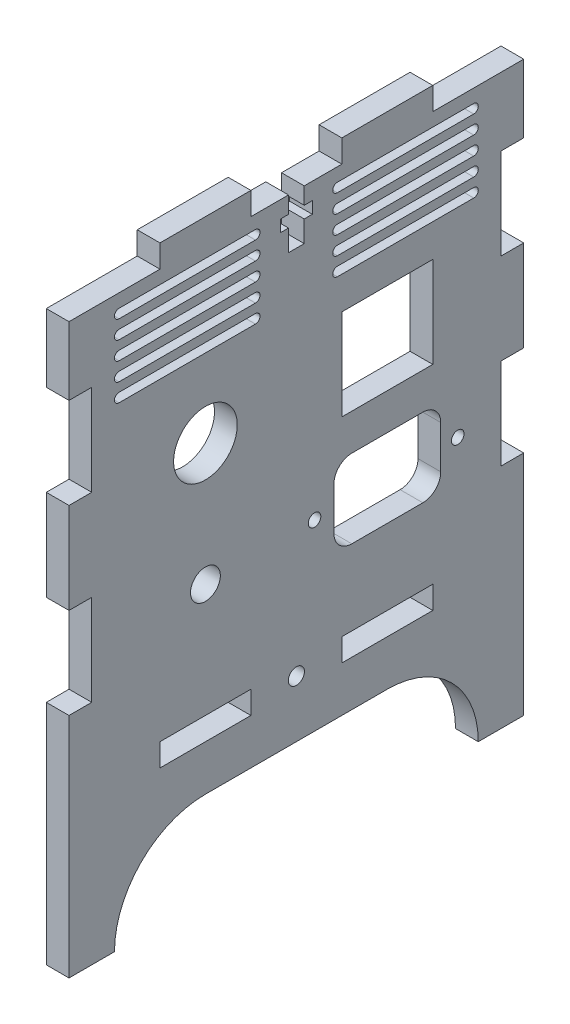
SolidWorks part; units mm, degrees
ref_plane "Front Plane" through (0, 0, 0) normal (0, 0, 1) x (1, 0, 0)
ref_plane "Top Plane" through (0, 0, 0) normal (0, 1, 0) x (1, 0, 0)
ref_plane "Right Plane" through (0, 0, 0) normal (1, 0, 0) x (0, 0, -1)
sketch "Sketch1" plane through (0, 0, 0) normal (1, 0, 0) x (0, 0, -1)
  line L1 (-63.5, 82.55) -> (63.5, 82.55)
  line L2 (-63.5, 82.55) -> (-63.5, -82.55)
  line L3 (-63.5, -82.55) -> (63.5, -82.55)
  line L4 (63.5, 82.55) -> (63.5, -82.55)
  line L5 (-63.5, 82.55) -> (63.5, -82.55) construction
  line L6 (-63.5, -82.55) -> (63.5, 82.55) construction
  point P0 (0, 0)
  dimension "D1" = 127
  dimension "D2" = 165.1
extrude "Boss-Extrude1" add sketch "Sketch1" along normal blind 6.35
sketch "Sketch2" plane through (6.35, 0, 0) normal (1, 0, 0) x (0, 0, -1)
  line L1 (-63.5, 82.55) -> (-38.1, 82.55)
  line L2 (-63.5, 82.55) -> (-63.5, 76.2)
  line L3 (-63.5, 76.2) -> (-38.1, 76.2)
  line L4 (-38.1, 82.55) -> (-38.1, 76.2)
  dimension "D1" = 25.4
  dimension "D2" = 6.35
extrude "Cut-Extrude1" cut sketch "Sketch2" against normal blind 6.35
pattern_linear "LPattern1" count 3 spacing 50.8 along (0, 0, -1) of "Cut-Extrude1"
sketch "Sketch5" plane through (6.35, 0, 0) normal (1, 0, 0) x (0, 0, -1)
  line L0 (-25.4, -82.55) -> (25.4, -82.55) construction
  line L1 (-63.5, -82.55) -> (63.5, -82.55) construction
  line L2 (-25.4, -57.15) -> (25.4, -57.15)
  line L3 (-25.4, -107.95) -> (25.4, -107.95)
  arc A0 (-25.4, -57.15) -> (-25.4, -107.95) centre (-25.4, -82.55) ccw
  arc A1 (25.4, -107.95) -> (25.4, -57.15) centre (25.4, -82.55) ccw
  point P4 (0, -82.55)
  dimension "D2" = 25.4
  dimension "D1" = 50.8
extrude "Cut-Extrude4" cut sketch "Sketch5" against normal blind 6.35
sketch "Sketch8" plane through (6.35, 0, 0) normal (1, 0, 0) x (0, 0, -1)
  line L0 (63.5, -82.55) -> (63.5, 76.2) construction
  line L1 (63.5, 57.15) -> (57.15, 57.15)
  line L2 (63.5, 57.15) -> (63.5, 31.75)
  line L3 (63.5, 31.75) -> (57.15, 31.75)
  line L4 (57.15, 57.15) -> (57.15, 31.75)
  line L5 (38.1, 82.55) -> (12.7, 82.55) construction
  dimension "D1" = 25.4
  dimension "D2" = 25.4
  dimension "D3" = 6.35
extrude "Cut-Extrude6" cut sketch "Sketch8" against normal blind 6.35
pattern_linear "LPattern4" count 2 spacing 50.8 along (0, -1, 0) of "Cut-Extrude6"
ref_plane "Plane1" through (0, 0, 0) normal (0, 0, 1) x (1, 0, 0)
mirror "Mirror1" about plane through (0, 0, 0) normal (0, 0, 1) of "LPattern4"
sketch "Sketch9" plane through (0, 0, 0) normal (-1, 0, 0) x (0, 0, 1)
  line L0 (-63.5, -82.55) -> (-63.5, -19.05) construction
  line L1 (-38.1, -38.1) -> (-12.7, -38.1)
  line L2 (-38.1, -38.1) -> (-38.1, -44.45)
  line L3 (-38.1, -44.45) -> (-12.7, -44.45)
  line L4 (-12.7, -38.1) -> (-12.7, -44.45)
  line L5 (-38.1, 82.55) -> (-12.7, 82.55) construction
  point P6 (-25.4, 82.55)
  dimension "D1" = 25.4
  dimension "D2" = 6.35
  dimension "D3" = 25.4
  dimension "D4" = 120.65
extrude "Cut-Extrude7" cut sketch "Sketch9" against normal blind 6.35
pattern_linear "LPattern6" count 2 spacing 50.8 along (0, 0, 1) of "Cut-Extrude7"
sketch "Sketch16" plane through (0, 0, 0) normal (-1, 0, 0) x (0, 0, 1)
  line L0 (12.7, 76.2) -> (-12.7, 76.2) construction
  line L1 (-2.1971, 76.2) -> (2.1971, 76.2)
  line L2 (-2.1971, 76.2) -> (-2.1971, 62.23)
  line L3 (-2.1971, 62.23) -> (2.1971, 62.23)
  line L4 (2.1971, 76.2) -> (2.1971, 62.23)
  line L5 (-12.7, 76.2) -> (-12.7, 82.55) construction
  line L7 (-4.445, 71.501) -> (4.445, 71.501)
  line L8 (-4.445, 71.501) -> (-4.445, 68.199)
  line L9 (-4.445, 68.199) -> (4.445, 68.199)
  line L10 (4.445, 71.501) -> (4.445, 68.199)
  point P6 (0, 62.23)
  point P13 (0, 71.501)
  point P14 (4.445, 69.85)
  dimension "D1" = 4.3942
  dimension "D2" = 13.97
  dimension "D3" = 12.7
  dimension "D4" = 3.302
  dimension "D5" = 8.89
  dimension "D6" = 12.7
  dimension "D7" = 6.35
extrude "Cut-Extrude14" cut sketch "Sketch16" against normal blind 6.35 contours L7 L10 L9 L8 | L1 L4 L3 L2
hole_wizard "#8 Clearance Hole1" positions "Sketch18" profile "Sketch17" hole size "#8" standard "ANSI Inch"
sketch "Sketch18" plane through (0, 0, 0) normal (-1, 0, 0) x (0, 0, 1)
  line L3 (-12.7, -44.45) -> (-12.7, -38.1) construction
  line L4 (38.1, -38.1) -> (12.7, -38.1) construction
  point P0 (0, -41.275)
  point P16 (-12.7, -41.275)
  dimension "D1" = 12.7
  dimension "D2" = 3.175
sketch "Sketch17" plane through (0, -41.275, 0) normal (0, 1, 0) x (0, 0, 1)
  line L0 (0, 0) -> (0, 11.5107)
  line L1 (0, 11.5107) -> (2.2479, 10.16)
  line L2 (2.2479, 10.16) -> (2.2479, 0)
  line L5 (2.2479, 0) -> (0, 0)
  line L10 (0, 11.5107) -> (-2.2479, 10.16) construction
  line L11 (0, -6.35) -> (0, 107.95) construction
  dimension "Hole Dia." = 4.4958
  dimension "Hole Depth" = 10.16
  dimension "Drill Angle" = 118
sketch "Sketch19" plane through (0, 0, 0) normal (-1, 0, 0) x (0, 0, 1)
  line L0 (-49.53, 71.1789) -> (-11.43, 71.1789) construction
  line L1 (-49.53, 72.4489) -> (-11.43, 72.4489)
  line L2 (-49.53, 69.9089) -> (-11.43, 69.9089)
  line L3 (-38.1, 82.55) -> (-38.1, 76.2) construction
  arc A0 (-49.53, 72.4489) -> (-49.53, 69.9089) centre (-49.53, 71.1789) ccw
  arc A1 (-11.43, 69.9089) -> (-11.43, 72.4489) centre (-11.43, 71.1789) ccw
  point P2 (-30.48, 71.1789)
  point P7 (-30.48, 72.4489)
  dimension "D2" = 1.27
  dimension "D1" = 38.1
  dimension "D3" = 7.62
extrude "Cut-Extrude15" cut sketch "Sketch19" against normal blind 6.35
mirror "Mirror2" about plane through (0, 0, 0) normal (0, 0, 1) of "Cut-Extrude15"
pattern_linear "LPattern7" count 5 spacing 5.08 along (0, -1, 0) of "Mirror2"
sketch "Sketch20" plane through (0, 0, 0) normal (-1, 0, 0) x (0, 0, 1)
  line L1 (-35.3225, 4.9) -> (-15.4775, 4.9)
  line L2 (-40.3225, -0.1) -> (-40.3225, -12.0202)
  line L3 (-35.3225, -17.0202) -> (-15.4775, -17.0202)
  line L4 (-10.4775, -0.1) -> (-10.4775, -12.0202)
  line L5 (-63.5, 6.35) -> (-63.5, 31.75) construction
  circle A0 centre (-45.0725, -6.0601) radius 1.75
  circle A1 centre (-5.0725, -6.0601) radius 1.75
  arc A2 (-40.3225, -12.0202) -> (-35.3225, -17.0202) centre (-35.3225, -12.0202) ccw
  arc A3 (-15.4775, 4.9) -> (-10.4775, -0.1) centre (-15.4775, -0.1) cw
  arc A4 (-15.4775, -17.0202) -> (-10.4775, -12.0202) centre (-15.4775, -12.0202) ccw
  arc A5 (-40.3225, -0.1) -> (-35.3225, 4.9) centre (-35.3225, -0.1) cw
  point P8 (-25.4, 4.9)
  point P13 (-40.3225, -6.0601)
  point P18 (-10.4775, 4.9)
  point P21 (-10.4775, -17.0202)
  point P24 (-40.3225, 4.9)
  dimension "D1" = 3.5
  dimension "D2" = 3.5
  dimension "D10" = 5
  dimension "D11" = 5
  dimension "D12" = 5
  dimension "D13" = 5
  dimension "D3" = 40
  dimension "D4" = 29.845
  dimension "D5" = 21.9202
  dimension "D6" = 38.1
extrude "Cut-Extrude16" cut sketch "Sketch20" against normal blind 7.62
sketch "Sketch22" plane through (0, 0, 0) normal (-1, 0, 0) x (0, 0, 1)
  line L0 (-15.4775, 4.9) -> (-35.3225, 4.9) construction
  line L1 (-38.1, 40.46) -> (-12.7, 40.46)
  line L2 (-38.1, 40.46) -> (-38.1, 15.06)
  line L3 (-38.1, 15.06) -> (-12.7, 15.06)
  line L4 (-12.7, 40.46) -> (-12.7, 15.06)
  point P4 (-25.4, 15.06)
  point P5 (-25.4, 4.9)
  dimension "D1" = 25.4
  dimension "D2" = 25.4
  dimension "D3" = 0
  dimension "D4" = 10.16
extrude "Cut-Extrude17" cut sketch "Sketch22" against normal blind 6.35
sketch "Sketch23" plane through (0, 0, 0) normal (-1, 0, 0) x (0, 0, 1)
  line L0 (-12.7, 15.06) -> (-12.7, 40.46) construction
  line L2 (63.5, 31.75) -> (63.5, 6.35) construction
  circle A0 centre (25.4, 27.76) radius 8.89
  point P2 (-12.7, 27.76)
  dimension "D1" = 17.78
  dimension "D2" = 0
  dimension "D3" = 38.1
extrude "Cut-Extrude18" cut sketch "Sketch23" against normal blind 7.62
sketch "Sketch24" plane through (0, 0, 0) normal (-1, 0, 0) x (0, 0, 1)
  line L1 (57.15, 6.35) -> (57.15, -19.05) construction
  circle A0 centre (25.4, -6.35) radius 4.1672
  circle A1 centre (25.4, 27.76) radius 8.89 construction
  point P4 (57.15, -6.35)
  dimension "D1" = 0
  dimension "D2" = 8.3344
  dimension "D3" = 0
extrude "Cut-Extrude19" cut sketch "Sketch24" against normal blind 7.62
